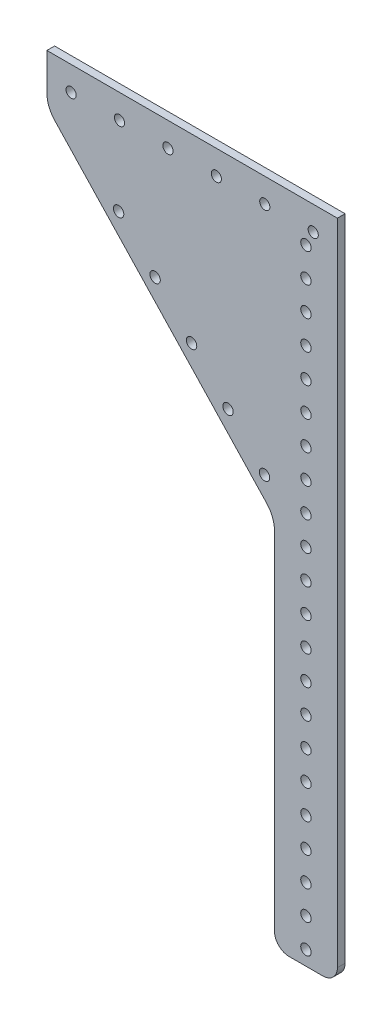
SolidWorks part; units mm, degrees
ref_plane "Front Plane" through (0, 0, 0) normal (0, 0, 1) x (1, 0, 0)
ref_plane "Top Plane" through (0, 0, 0) normal (0, 1, 0) x (1, 0, 0)
ref_plane "Right Plane" through (0, 0, 0) normal (1, 0, 0) x (0, 0, -1)
sketch "Sketch1" plane through (0, 0, 0) normal (0, 0, 1) x (1, 0, 0)
  line L0 (26, 274.1) -> (26, 0)
  line L1 (0, 0) -> (26, 0)
  line L2 (0, 0) -> (0, 254.1) construction
  line L5 (0, 254.1) -> (-94, 254.1) construction
  line L7 (26, 274.1) -> (-94, 274.1)
  line L8 (-94, 254.1) -> (-94, 274.1)
  line L9 (-94, 264.1) -> (26, 264.1) construction
  line L10 (-94, 254.1) -> (0, 154.1)
  line L11 (0, 154.1) -> (0, 0)
  line L12 (-85.7653, 254.1) -> (0, 162.8603) construction
  line L13 (-64.3815, 231.3513) -> (-79.4496, 247.3811) construction
  line L14 (13, 210) -> (13, 222) construction
  circle A0 centre (13, 6) radius 2.15
  circle A1 centre (13, 18) radius 2.15
  circle A2 centre (13, 30) radius 2.15
  circle A3 centre (13, 42) radius 2.15
  circle A4 centre (13, 54) radius 2.15
  circle A5 centre (13, 66) radius 2.15
  circle A6 centre (13, 78) radius 2.15
  circle A7 centre (13, 90) radius 2.15
  circle A8 centre (13, 102) radius 2.15
  circle A9 centre (13, 114) radius 2.15
  circle A10 centre (13, 126) radius 2.15
  circle A11 centre (13, 138) radius 2.15
  circle A12 centre (13, 150) radius 2.15
  circle A13 centre (13, 162) radius 2.15
  circle A14 centre (13, 174) radius 2.15
  circle A15 centre (13, 186) radius 2.15
  circle A16 centre (13, 198) radius 2.15
  circle A17 centre (13, 210) radius 2.15
  circle A19 centre (16, 264.1) radius 2.1
  circle A20 centre (-4, 264.1) radius 2.1
  circle A21 centre (-24, 264.1) radius 2.1
  circle A22 centre (-44, 264.1) radius 2.1
  circle A23 centre (-64, 264.1) radius 2.1
  circle A24 centre (-4.1095, 167.232) radius 2.15
  circle A25 centre (-19.1775, 183.2618) radius 2.15
  circle A26 centre (-34.2455, 199.2917) radius 2.15
  circle A27 centre (-49.3135, 215.3215) radius 2.15
  circle A28 centre (-64.3815, 231.3513) radius 2.15
  circle A29 centre (-79.4496, 247.3811) radius 2.15 construction
  circle A30 centre (13, 222) radius 2.15
  circle A31 centre (13, 234) radius 2.15
  circle A32 centre (13, 246) radius 2.15
  circle A33 centre (13, 258) radius 2.15
  circle A34 centre (13, 270) radius 2.15 construction
  circle A35 centre (-84, 264.1) radius 2.1
  dimension "D5" = 4.3
  dimension "D7" = 10
  dimension "D8" = 4.2
  dimension "D11" = 4.3
  dimension "D21" = 4.2
  dimension "D1" = 26
  dimension "D2" = 20
  dimension "D3" = 120
  dimension "D4" = 274.1
  dimension "D6" = 6
  dimension "D9" = 10
  dimension "D10" = 6
  dimension "D12" = 6
  dimension "D13" = 22
  dimension "D14" = 100
  dimension "D15" = 5
  dimension "D17" = 22
  dimension "D18" = 18
  dimension "D19" = 12
  dimension "D22" = 20
  dimension "D16" = 2
  dimension "D20" = 6
extrude "Boss-Extrude1" add sketch "Sketch1" along normal blind 3.175
fillet "Fillet2" radius 12 2 edges at (0, 154.1, 1.5875) (-94, 254.1, 1.5875)
fillet "Fillet3" radius 6 2 edges at (26, 0, 1.5875) (0, 0, 1.5875)
